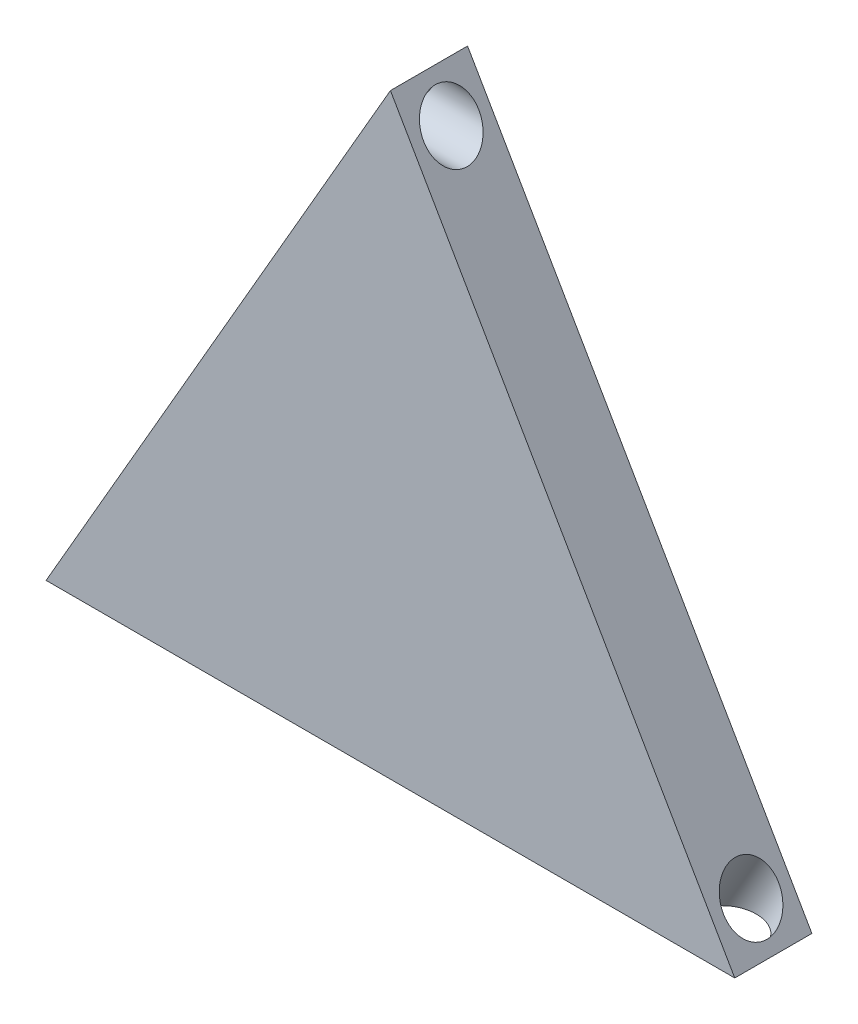
SolidWorks part; units mm, degrees
ref_plane "Front Plane" through (0, 0, 0) normal (0, 0, 1) x (1, 0, 0)
ref_plane "Top Plane" through (0, 0, 0) normal (0, 1, 0) x (1, 0, 0)
ref_plane "Right Plane" through (0, 0, 0) normal (1, 0, 0) x (0, 0, -1)
sketch "Sketch1" plane through (0, 0, 0) normal (0, 0, 1) x (1, 0, 0)
  line L0 (-42.8571, 0) -> (82.1429, 0)
  line L1 (82.1429, 0) -> (19.6429, 108.2532)
  line L2 (19.6429, 108.2532) -> (-42.8571, 0)
  dimension "D1" = 125
  dimension "D2" = 125
  dimension "D3" = 125
extrude "Boss-Extrude1" add sketch "Sketch1" along normal blind 14
sketch "Sketch2" plane through (0, 0, 0) normal (1, 0, 0) x (0, 0, -1)
  line L0 (-14, 108.2532) -> (0, 108.2532) construction
  line L1 (0, 108.2532) -> (0, 94.2532) construction
  line L2 (0, 0) -> (0, 108.2532) construction
  line L3 (0, 94.2532) -> (-14, 108.2532) construction
  circle A0 centre (-7, 101.2532) radius 5
  dimension "D2" = 10
  dimension "D1" = 14
extrude "Cut-Extrude1" cut sketch "Sketch2" along normal blind 50
ref_plane "Plane1" through (-10.7143, 18.5577, 0) normal (0.5, -0.866, 0) x (-0.866, -0.5, 0)
sketch "Sketch5" plane through (-10.7143, 18.5577, 0) normal (0.5, -0.866, 0) x (-0.866, -0.5, 0)
  line L0 (37.1154, -14) -> (37.1154, 0) construction
  line L1 (37.1154, 0) -> (23.1154, 0) construction
  line L2 (37.1154, 0) -> (-71.1378, 0) construction
  line L3 (23.1154, 0) -> (37.1154, -14) construction
  circle A0 centre (30.1154, -7) radius 5
  dimension "D2" = 10
  dimension "D1" = 14
extrude "Cut-Extrude3" cut sketch "Sketch5" against normal blind 50 and the other way blind 50
ref_plane "Plane2" through (20.5357, 35.5689, 0) normal (0.5, 0.866, 0) x (0.866, -0.5, 0)
sketch "Sketch6" plane through (20.5357, 35.5689, 0) normal (0.5, 0.866, 0) x (0.866, -0.5, 0)
  line L0 (71.1378, -14) -> (71.1378, 0) construction
  line L1 (71.1378, 0) -> (57.1378, 0) construction
  line L2 (71.1378, 0) -> (-37.1154, 0) construction
  line L3 (57.1378, 0) -> (71.1378, -14) construction
  circle A0 centre (64.1378, -7) radius 5
  dimension "D2" = 10
  dimension "D1" = 14
extrude "Cut-Extrude4" cut sketch "Sketch6" against normal blind 50 and the other way blind 50
